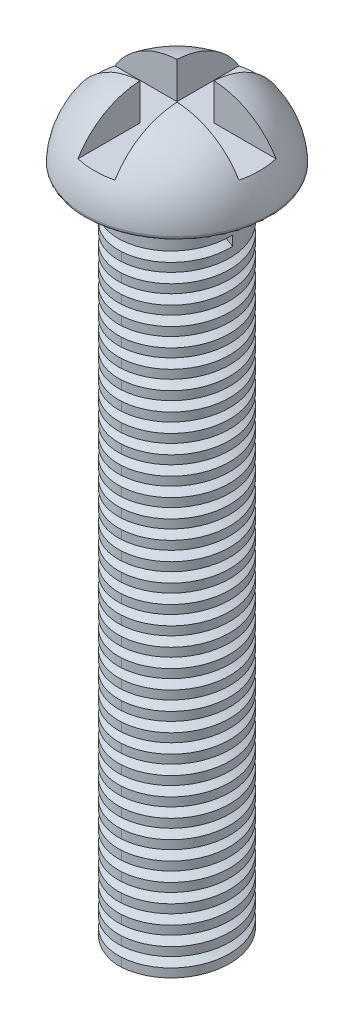
SolidWorks part; units mm, degrees
ref_plane "前视基准面" through (0, 0, 0) normal (0, 0, 1) x (1, 0, 0)
ref_plane "上视基准面" through (0, 0, 0) normal (0, 1, 0) x (1, 0, 0)
ref_plane "右视基准面" through (0, 0, 0) normal (1, 0, 0) x (0, 0, -1)
sketch "草图1" plane through (0, 0, 0) normal (0, 1, 0) x (1, 0, 0)
  circle A0 centre (0, 0) radius 1.5
  dimension "D1" = 3
extrude "凸台-拉伸1" add sketch "草图1" against normal blind 18
sketch "草图2" plane through (0, 0, 0) normal (0, 1, 0) x (1, 0, 0)
  circle A0 centre (0, 0) radius 2.5
  dimension "D1" = 5
extrude "凸台-拉伸2" add sketch "草图2" along normal blind 2
fillet "圆角1" radius 2 1 edges at (0, 2, 2.5)
sketch "草图3" plane through (0, 2, 0) normal (0, 1, 0) x (1, 0, 0)
  line L0 (2.5, 0.5) -> (-2.5, 0.5)
  line L1 (-0.5, 2.5) -> (0.5, 2.5)
  line L2 (-0.5, 2.5) -> (-0.5, -2.5)
  line L3 (-0.5, -2.5) -> (0.5, -2.5)
  line L4 (0.5, 2.5) -> (0.5, -2.5)
  line L5 (-0.5, 2.5) -> (0.5, -2.5) construction
  line L6 (-0.5, -2.5) -> (0.5, 2.5) construction
  line L7 (2.5, 0.5) -> (2.5, -0.5)
  line L8 (2.5, -0.5) -> (-2.5, -0.5)
  line L9 (-2.5, 0.5) -> (-2.5, -0.5)
  circle A0 centre (0, 0) radius 0.5 construction
  circle A1 centre (0, 0) radius 2.5 construction
  point P0 (0, 0)
  point P6 (0.5, 0)
  point P9 (-0.5, 0)
  point P10 (0, -0.5)
  point P11 (0, 0.5)
  point P17 (0, 2.5)
  circle M9 centre (0, 0) radius 0.5
  dimension "D1" = 2
extrude "切除-拉伸1" cut sketch "草图3" against normal blind 1 contours L4 L1 L2 L0 | L8 L7 L0 L4 | L0 L9 L8 L2 | M9 | L4 L8 L2 L3 | L4 L0 M9 | L8 L4 M9 | L0 L2 M9 | L8 L2 M9 region at (1.5, 2, 0) region at (0.3883, 2, -0.3883) region at (0, 2, -1.5) region at (-0.3883, 2, -0.3883) region at (0, 2, 0) region at (0.3883, 2, 0.3883) region at (0, 2, 1.5) region at (-1.5, 2, 0) region at (-0.3883, 2, 0.3883)
fillet "圆角2" radius 0.1 1 edges at (0, 0, 2.5)
sketch "草图4" plane through (0, -18, 0) normal (0, -1, 0) x (1, 0, 0)
  circle A1 centre (0, 0) radius 1.5
curve "螺旋线/涡状线1" pitch 0.5 height 17 radius 1.5 centre (0, -18, 0) axis (0, 1, 0) start towards (1, 0, 0)
sketch "草图19" plane through (0, 0, 0) normal (0, 0, 1) x (1, 0, 0)
  line L1 (1.2691, -18) -> (1.6155, -18.2)
  line L2 (1.6155, -18.2) -> (1.6155, -17.8)
  line L3 (1.6155, -17.8) -> (1.2691, -18)
  circle A0 centre (1.5, -18) radius 0.1155 construction
  dimension "D1" = 0.4
sweep "切除-扫描3" cut profiles "草图19" path "螺旋线/涡状线1" align with end faces yes
